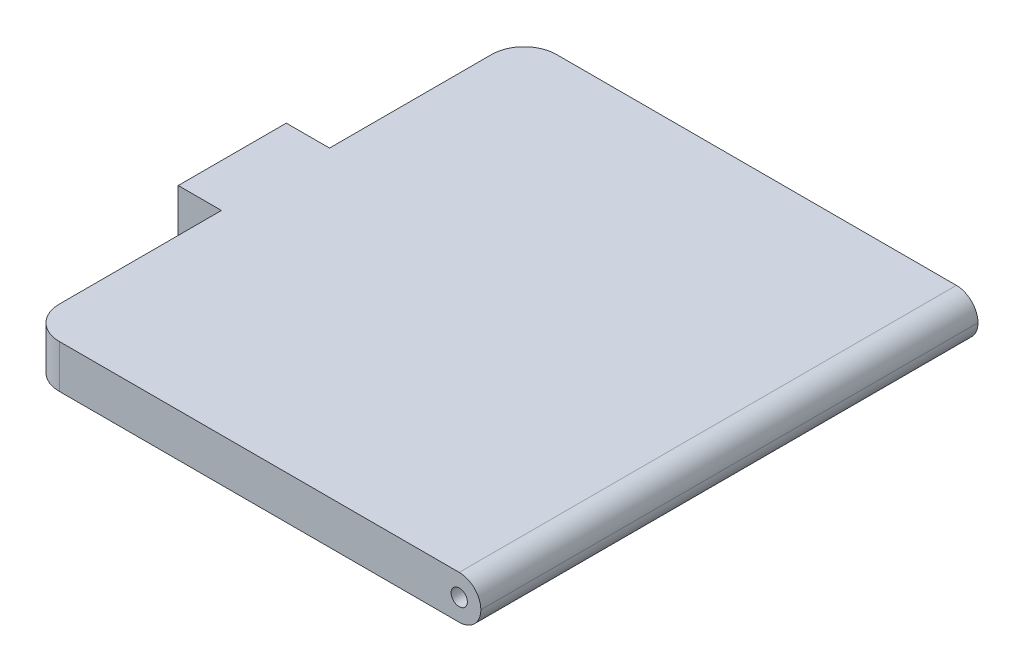
SolidWorks part; units mm, degrees
ref_plane "Front Plane" through (0, 0, 0) normal (0, 0, 1) x (1, 0, 0)
ref_plane "Top Plane" through (0, 0, 0) normal (0, 1, 0) x (1, 0, 0)
ref_plane "Right Plane" through (0, 0, 0) normal (1, 0, 0) x (0, 0, -1)
sketch "Sketch1" plane through (0, 0, 0) normal (0, 1, 0) x (1, 0, 0)
  line L0 (-65.1127, 0) -> (0, 0) construction
  line L1 (0, -38.6972) -> (0, 46.1351) construction
  line L2 (-1, 23) -> (-1, -23)
  line L3 (-1, -23) -> (-40, -23)
  line L5 (-1, 23) -> (-40, 23)
  line L6 (-43, -20) -> (-43, 20)
  line L9 (0, 0) -> (-43, -23) construction
  line L11 (0, 0) -> (-43, 23) construction
  arc A2 (-40, -23) -> (-43, -20) centre (-40, -20) cw
  arc A3 (-40, 23) -> (-43, 20) centre (-40, 20) ccw
  point P5 (0, 0)
  dimension "D4" = 1
extrude "Boss-Extrude1" add sketch "Sketch1" along normal blind 4
fillet "Fillet1" radius 2 2 edges at (-1, 0, 0) (-1, 4, 0)
sketch "Sketch2" plane through (0, 0, 23) normal (0, 0, 1) x (1, 0, 0)
  circle A0 centre (-3, 2) radius 0.75
  dimension "D1" = 1.5
extrude "Cut-Extrude1" cut sketch "Sketch2" against normal up to surface (46 mm away) up to face at (-17.2343, 2, -23)
sketch "Sketch4" plane through (-43, 0, 0) normal (-1, 0, 0) x (0, 0, 1)
  line L0 (0, -2.6222) -> (0, 8.3232) construction
  line L1 (-5, 4) -> (-5, 0) construction
  line L2 (-20, 4) -> (20, 4) construction
  line L3 (-20, 0) -> (20, 0) construction
  line L4 (5, 4) -> (5, 0) construction
  line L5 (-5, 1) -> (5, 1) construction
  line L6 (-5, 1) -> (-5, 4)
  line L7 (-5, 4) -> (5, 4)
  line L8 (5, 4) -> (5, 1)
  line L9 (5, 1) -> (-5, 1)
  point P9 (0, 2.8505)
  dimension "D1" = 5
  dimension "D2" = 3
extrude "Boss-Extrude2" add sketch "Sketch4" along normal blind 4
sketch "Sketch6" plane through (0, 1, 0) normal (0, -1, 0) x (1, 0, 0)
  line L0 (-47, -5) -> (-47, 5)
  line L1 (-47, 5) -> (-45, 5)
  line L2 (-47, 5) -> (-43, 5) construction
  line L3 (-45, 5) -> (-45, -5)
  line L4 (-47, -5) -> (-43, -5) construction
  line L5 (-45, -5) -> (-47, -5)
extrude "Boss-Extrude3" add sketch "Sketch6" along normal blind 5
